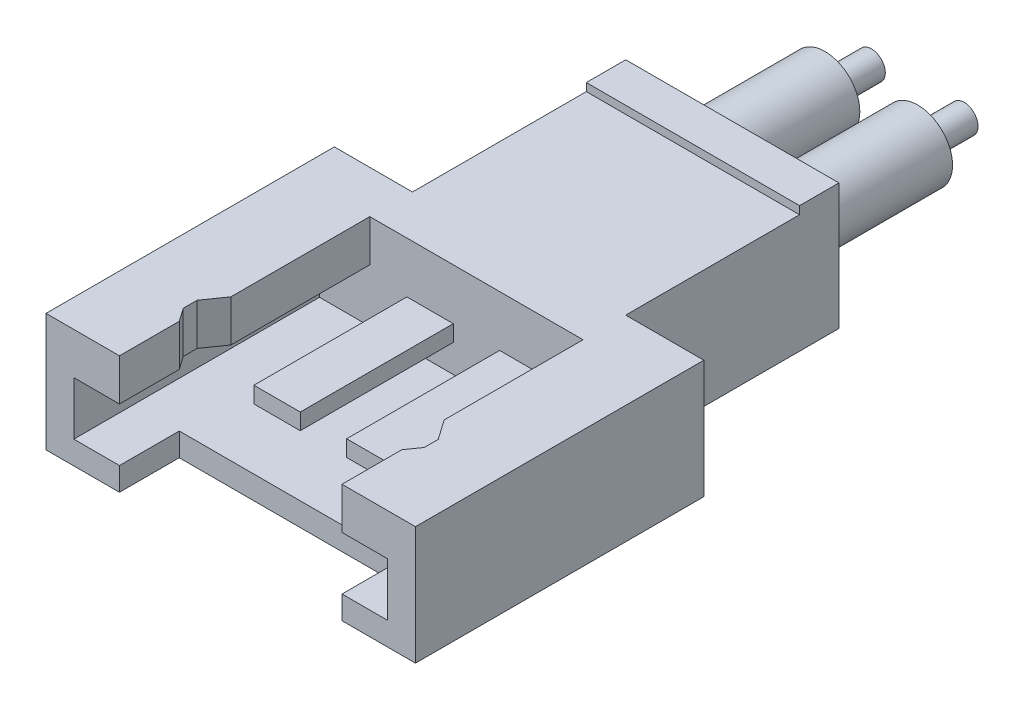
SolidWorks part; units mm, degrees
ref_plane "Front Plane" through (0, 0, 0) normal (0, 0, 1) x (1, 0, 0)
ref_plane "Top Plane" through (0, 0, 0) normal (0, 1, 0) x (1, 0, 0)
ref_plane "Right Plane" through (0, 0, 0) normal (1, 0, 0) x (0, 0, -1)
sketch "Sketch1" plane through (0, 0, 0) normal (0, 0, 1) x (1, 0, 0)
  line L1 (-2.3, 1.275) -> (2.3, 1.275)
  line L2 (-2.3, 1.275) -> (-2.3, -1.275)
  line L3 (-2.3, -1.275) -> (2.3, -1.275)
  line L4 (2.3, 1.275) -> (2.3, -1.275)
  line L5 (-2.3, 1.275) -> (2.3, -1.275) construction
  line L6 (-2.3, -1.275) -> (2.3, 1.275) construction
  point P0 (0, 0)
  dimension "D1" = 4.6
  dimension "D2" = 2.55
extrude "Boss-Extrude1" add sketch "Sketch1" along normal blind 4.6
sketch "Sketch2" plane through (0, 0, 4.6) normal (0, 0, 1) x (1, 0, 0)
  line L0 (2.3, 1.275) -> (-2.3, 1.275) construction
  line L1 (-3.985, 1.275) -> (3.985, 1.275)
  line L2 (-3.985, 1.275) -> (-3.985, -1.275)
  line L3 (-3.985, -1.275) -> (3.985, -1.275)
  line L4 (3.985, 1.275) -> (3.985, -1.275)
  line L5 (-3.985, 1.275) -> (3.985, -1.275) construction
  line L6 (-3.985, -1.275) -> (3.985, 1.275) construction
  point P0 (0, 0)
  dimension "D1" = 7.97
extrude "Boss-Extrude2" add sketch "Sketch2" along normal blind 6.22
sketch "Sketch3" plane through (0, 1.275, 0) normal (0, 1, 0) x (1, 0, 0)
  line L0 (2.3, -4.6) -> (2.3, 0) construction
  line L1 (-2.3, 0) -> (2.3, 0)
  line L2 (-2.3, 0) -> (-2.3, -0.85)
  line L3 (-2.3, -0.85) -> (2.3, -0.85)
  line L4 (2.3, 0) -> (2.3, -0.85)
  dimension "D1" = 0.85
extrude "Boss-Extrude3" add sketch "Sketch3" along normal offset from surface (0.17 mm away) 2.72 up to face at (0, -1.275, 5.005)
sketch "Sketch4" plane through (0, 0, 10.82) normal (0, 0, 1) x (1, 0, 0)
  line L0 (-3.985, -1.275) -> (3.985, -1.275) construction
  line L1 (-2.4, 1.275) -> (2.4, 1.275)
  line L2 (-2.4, 1.275) -> (-2.4, -1.275)
  line L3 (-2.4, -1.275) -> (2.4, -1.275)
  line L4 (2.4, 1.275) -> (2.4, -1.275)
  line L5 (-2.4, 1.275) -> (2.4, -1.275) construction
  line L6 (-2.4, -1.275) -> (2.4, 1.275) construction
  point P0 (0, 0)
  dimension "D1" = 4.8
extrude "Cut-Extrude1" cut sketch "Sketch4" against normal blind 1.29
sketch "Sketch5" plane through (0, 0, 10.82) normal (0, 0, 1) x (1, 0, 0)
  line L0 (0, 1.275) -> (0, -1.275) construction
  line L1 (-2.3, 1.275) -> (2.3, 1.275) construction
  line L2 (-2.4, -1.275) -> (2.4, -1.275) construction
  line L3 (-3.985, -1.275) -> (-2.4, -1.275) construction
  line L4 (-3.385, 0.375) -> (3.385, 0.375)
  line L5 (-3.385, 0.375) -> (-3.385, -0.775)
  line L6 (-3.385, -0.775) -> (3.385, -0.775)
  line L7 (3.385, 0.375) -> (3.385, -0.775)
  line L8 (-3.385, 0.375) -> (3.385, -0.775) construction
  line L9 (-3.385, -0.775) -> (3.385, 0.375) construction
  line L10 (-3.985, 1.275) -> (-3.985, -1.275) construction
  line L11 (-2.4, 1.275) -> (-3.985, 1.275) construction
  point P6 (0, -0.2)
  dimension "D1" = 0.5
  dimension "D2" = 0.6
  dimension "D3" = 0.9
extrude "Cut-Extrude2" cut sketch "Sketch5" against normal blind 5.3
sketch "Sketch6" plane through (0, 1.275, 0) normal (0, 1, 0) x (1, 0, 0)
  line L0 (0, -0.85) -> (0, -9.53) construction
  line L1 (-2.3, -0.85) -> (2.3, -0.85) construction
  line L2 (2.4, -9.53) -> (-2.4, -9.53) construction
  line L3 (-3.385, -5.52) -> (3.385, -5.52) construction
  line L4 (2.3, -5.52) -> (-2.3, -5.52)
  line L5 (2.3, -5.52) -> (2.3, -9.53)
  line L6 (2.3, -9.53) -> (-2.3, -9.53)
  line L7 (-2.3, -5.52) -> (-2.3, -9.53)
  line L8 (2.3, -5.52) -> (-2.3, -9.53) construction
  line L9 (2.3, -9.53) -> (-2.3, -5.52) construction
  line L10 (-2.4, -9.53) -> (-2.6, -9.2444)
  line L11 (-2.6, -9.2444) -> (-2.6, -8.9444)
  line L12 (-2.6, -8.9444) -> (-2.3, -8.5159)
  line L13 (-2.6, -9.0944) -> (-2.3, -9.0944) construction
  line L14 (-2.4, -9.53) -> (-2.3, -9.53)
  line L15 (2.6, -8.9444) -> (2.3, -8.5159)
  line L16 (2.6, -9.2444) -> (2.6, -8.9444)
  line L17 (2.4, -9.53) -> (2.6, -9.2444)
  line L18 (2.4, -9.53) -> (2.3, -9.53)
  point P6 (0, -7.525)
  point P20 (0, 0)
  line M3 (-2.4, -9.53) -> (2.4, -9.53)
  dimension "D1" = 4.6
  dimension "D2" = 0.3
  dimension "D3" = 145
  dimension "D4" = 0.3
extrude "Cut-Extrude3" cut sketch "Sketch6" against normal up to next contours L4 L7 L5 M3 | L12 L11 L10 L7 M3 | L17 L16 L15 L5 M3 region at (0, 1.275, 7.525) region at (2.4235, 1.275, 9.078) region at (-2.4235, 1.275, 9.078)
sketch "Sketch7" plane through (0, 0, 5.52) normal (0, 0, 1) x (1, 0, 0)
  line L0 (-3.985, 0) -> (3.985, 0) construction
  line L1 (-3.985, 1.275) -> (-3.985, -1.275) construction
  line L2 (3.985, -1.275) -> (3.985, 1.275) construction
  line L3 (0, 1.445) -> (0, -1.275) construction
  line L4 (-2.3, 1.445) -> (2.3, 1.445) construction
  line L5 (-2.4, -1.275) -> (2.4, -1.275) construction
  line L6 (1.5, 0.175) -> (1.5, -0.175)
  line L7 (-1.5, 0.175) -> (-0.5, 0.175)
  line L8 (-1.5, 0.175) -> (-1.5, -0.175)
  line L9 (-1.5, -0.175) -> (-0.5, -0.175)
  line L10 (-0.5, 0.175) -> (-0.5, -0.175)
  line L11 (-1.5, 0.175) -> (-0.5, -0.175) construction
  line L12 (-1.5, -0.175) -> (-0.5, 0.175) construction
  line L13 (1.5, 0.175) -> (0.5, 0.175)
  line L14 (0.5, 0.175) -> (0.5, -0.175)
  line L15 (1.5, -0.175) -> (0.5, -0.175)
  point P12 (-1, 0)
  dimension "D1" = 0.35
  dimension "D2" = 1
  dimension "D3" = 2
extrude "Boss-Extrude4" add sketch "Sketch7" along normal offset from surface (3.3 mm away) 2 up to face at (-3.0425, -0.1, 10.82)
sketch "Sketch8" plane through (0, 0, 0) normal (0, 0, -1) x (-1, 0, 0)
  line L0 (-3.985, 0) -> (3.985, 0) construction
  line L1 (-3.985, -1.275) -> (-3.985, 1.275) construction
  line L2 (3.985, 1.275) -> (3.985, -1.275) construction
  line L3 (0, 1.445) -> (0, -1.275) construction
  line L4 (-2.3, 1.445) -> (2.3, 1.445) construction
  line L5 (2.3, -1.275) -> (-2.3, -1.275) construction
  circle A0 centre (-1, 0) radius 0.75
  circle A1 centre (1, 0) radius 0.75
  dimension "D2" = 1.5
  dimension "D1" = 2
extrude "Boss-Extrude5" add sketch "Sketch8" along normal blind 3
sketch "Sketch9" plane through (0, 0, -3) normal (0, 0, -1) x (-1, 0, 0)
  circle A0 centre (-1, 0) radius 0.3
  circle A1 centre (1, 0) radius 0.3
  dimension "D1" = 0.6
extrude "Boss-Extrude6" add sketch "Sketch9" along normal blind 1
